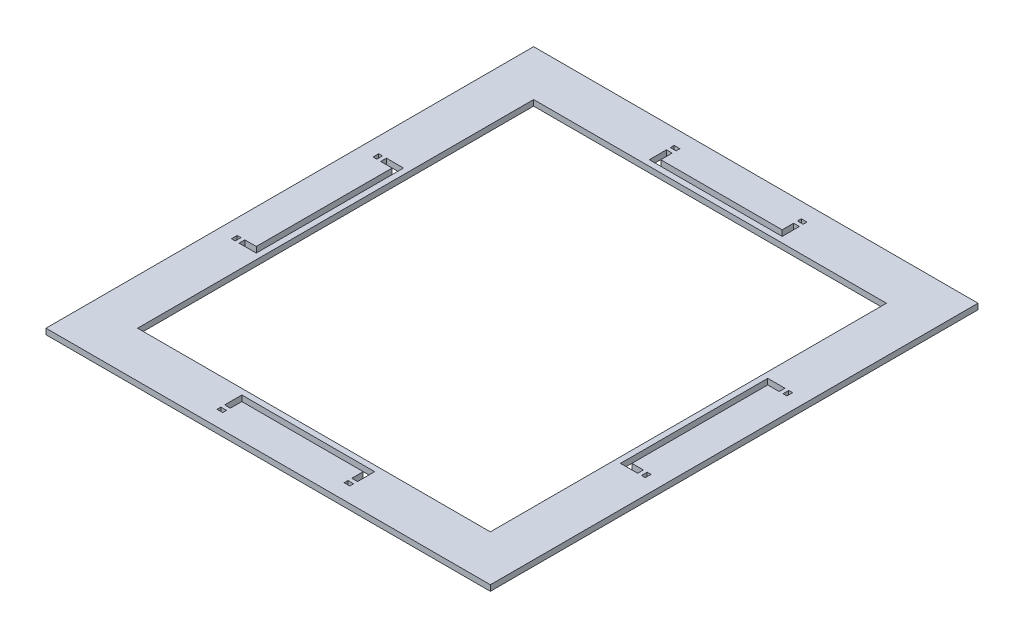
SolidWorks part; units mm, degrees
material "Delrin 2700 NC010, Low Viscosity Acetal Copolymer (SS)"
ref_plane "Front Plane" through (0, 0, 0) normal (0, 0, 1) x (1, 0, 0)
ref_plane "Top Plane" through (0, 0, 0) normal (0, 1, 0) x (1, 0, 0)
ref_plane "Right Plane" through (0, 0, 0) normal (1, 0, 0) x (0, 0, -1)
sketch "Sketch1" plane through (0, 0, 0) normal (0, 1, 0) x (1, 0, 0)
  line L0 (0, 135.225) -> (0, 0)
  line L1 (-110.525, 122.525) -> (0, 122.525)
  line L2 (-36.8417, 126.7583) -> (-33.6667, 126.7583)
  line L3 (-123.225, 135.225) -> (0, 135.225)
  line L4 (-123.225, 135.225) -> (-123.225, 0)
  line L5 (-36.8417, 126.7583) -> (-36.8417, 124.6417)
  line L6 (-36.8417, 124.6417) -> (-33.6667, 124.6417)
  line L7 (-33.6667, 126.7583) -> (-33.6667, 124.6417)
  line L8 (-114.7583, 40.8417) -> (-112.6417, 40.8417)
  line L9 (-114.7583, 40.8417) -> (-114.7583, 37.6667)
  line L10 (-114.7583, 37.6667) -> (-112.6417, 37.6667)
  line L11 (-112.6417, 40.8417) -> (-112.6417, 37.6667)
  line L12 (-110.525, 0) -> (-110.525, 122.525)
  line L13 (-110.525, 0) -> (-104.175, 0)
  line L14 (-110.525, 0) -> (-110.525, 37.6667)
  line L15 (-110.525, 37.6667) -> (-104.175, 37.6667)
  line L16 (-104.175, 0) -> (-104.175, 37.6667)
  line L17 (-110.525, 40.8417) -> (-101, 40.8417)
  line L18 (-110.525, 40.8417) -> (-110.525, 122.525)
  line L19 (-110.525, 122.525) -> (-78.9277, 122.525)
  line L20 (-101, 40.8417) -> (-101, 113)
  line L21 (-36.8417, 122.525) -> (-78.9277, 122.525)
  line L22 (-36.8417, 122.525) -> (-36.8417, 113)
  line L23 (-36.8417, 113) -> (-101, 113)
  line L24 (0, 122.525) -> (-33.6667, 122.525)
  line L25 (0, 122.525) -> (0, 116.175)
  line L26 (0, 116.175) -> (-33.6667, 116.175)
  line L27 (-33.6667, 122.525) -> (-33.6667, 116.175)
  line L28 (0, 0) -> (-123.225, 0)
  point P12 (0, 122.525)
  dimension "D1" = 12.7
  dimension "D2" = 2.1167
  dimension "D3" = 3.175
  dimension "D4" = 2.1167
  dimension "D5" = 2.1167
  dimension "D6" = 3.175
  dimension "D7" = 9.525
  dimension "D8" = 0
  dimension "D9" = 0
  dimension "D10" = 0
  dimension "D11" = 6.35
  dimension "D12" = 0
  dimension "D13" = 9.525
  dimension "D14" = 12.7
  dimension "D15" = 2.1167
  dimension "D16" = 6.35
  dimension "D17" = 104.175
  dimension "D18" = 67.3333
  dimension "D19" = 75.3333
  dimension "D21" = 116.175
extrude "Boss-Extrude1" add sketch "Sketch1" along normal blind 3.175 contours L28 L12 L1 L0 L3 L4 L8 L11 L10 L9 L2 L7 L6 L5 | L13 L16 L15 L12 | L23 L22 L1 L12 L17 L20 | L1 L27 L26 L0 region at (-1.8295, 0, -128.875) region at (-16.8333, 0, -119.35) region at (-37.9417, 0, -117.7625) region at (-107.35, 0, -18.8333)
sketch "Sketch3" plane through (0, 3.175, 0) normal (0, 1, 0) x (1, 0, 0)
  line L0 (0, 135.225) -> (0, 116.175) construction
  line L1 (-101, 113) -> (0, 113)
  line L2 (-101, 113) -> (-101, 109.825)
  line L3 (-101, 109.825) -> (0, 109.825)
  line L4 (0, 113) -> (0, 109.825)
  line L5 (-101, 113) -> (-97.825, 113)
  line L6 (-101, 113) -> (-101, 0)
  line L7 (-101, 0) -> (-97.825, 0)
  line L8 (-97.825, 113) -> (-97.825, 0)
  dimension "D1" = 3.175
  dimension "D2" = 3.175
  dimension "D3" = 0
  dimension "D4" = 0
extrude "Boss-Extrude2" add sketch "Sketch3" against normal blind 3.175 contours L5 L8 L7 L6 | L1 L4 L3 L2
mirror "Mirror4" about plane through (0, 0, 0) normal (1, 0, 0) of "Boss-Extrude2", "Boss-Extrude1"
mirror "Mirror5" about plane through (0, 0, 0) normal (0, 0, 1) of "Mirror4"
equation "\"D4@Sketch1\"=\"D2@Sketch1\""
equation "\"D15@Sketch1\"=\"D2@Sketch1\""
equation "\"D5@Sketch1\"=\"D2@Sketch1\""
equation "\"D6@Sketch1\"=\"D3@Sketch1\""
equation "\"D16@Sketch1\"=\"D11@Sketch1\""
equation "\"D13@Sketch1\"=\"D7@Sketch1\""
equation "\"Resolution Projector X\"= 1920"
equation "\"Resolution Projector Y\"= 1080"
equation "\"Resolution Build\"= 0.1"
equation "\"Size Build Volume X\"= \"Resolution Projector X\" * \"Resolution Build\""
equation "\"Size Build Volume Y\"= 2 * \"Resolution Projector Y\" * \"Resolution Build\""
equation "\"Size Build Volume Z\"= \"Size Build Volume Y\""
equation "\"Size Enclosure Internal X\"= 350mm"
equation "\"Size Enclosure Internal Y\"= \"Size Enclosure Internal X\""
equation "\"Size Enclosure Internal Z\"= \"Size Enclosure Internal X\""
equation "\"Size Enclosure External Z\"= 1000mm"
equation "\"Clearance Vat\"= 10mm'd_ clearance vat data"
equation "\"Size Vat X\"= \"Size Build Volume X\" + \"Clearance Vat\"'f_ size vat data"
equation "\"Size Vat Y\"= \"Size Build Volume Y\" + \"Clearance Vat\"'f_ size vat data"
equation "\"Size Vat Z\"= \"Size Build Volume Z\" + \"Clearance Vat\"'f_ size vat data"
equation "\"Thickness Vat\"= 3.175mm'g_ thickness vat data"
equation "\"width rib\"= 2 * \"Thickness Vat\"'g_ thickness of the Rib"
equation "\"width Lip on rib\"= \"Thickness Vat\" * 2'g_ thickness of the lip connected to the tab"
equation "\"height Lip on rib\"= \"width Lip on rib\"'g_ height of lip on rib structure"
equation "\"height adjustment\"= \"Thickness Vat\" * 2'g_ height adjustment for lip.  This flushes the top part of the tab to top of the walls"
equation "\"goofy tab x\"= \"Size Vat X\" * ( 1 / 3 ) - \"width rib\"'h_ goofy slot found on rib X"
equation "\"goofy tab y\"= \"Size Vat Y\" * ( 1 / 3 ) - \"width rib\"'h_ goofy slot found on rib Y"
equation "\"D3@Sketch1\"=\"Thickness Vat\""
equation "\"D18@Sketch1\"=\"Size Vat X\"/3"
equation "\"D19@Sketch1\"=\"Size Vat Y\"/3"
equation "\"D1@Sketch1\"=\"width Lip on rib\"*2mm"
equation "\"D14@Sketch1\"=\"D1@Sketch1\""
equation "\"D11@Sketch1\"=\"Thickness Vat\"*2"
equation "\"D7@Sketch1\"=\"Thickness Vat\"*3"
equation "\"D17@Sketch1\"=\"Size Vat X\"/2 + \"Thickness Vat\""
equation "\"D21@Sketch1\"=\"Size Vat Y\"/2 + \"Thickness Vat\""
equation "\"D1@Boss-Extrude1\"=\"Thickness Vat\""
equation "\"D1@Sketch3\"=\"Thickness Vat\""
equation "\"D2@Sketch3\"=\"Thickness Vat\""
equation "\"D1@Boss-Extrude2\"=\"Thickness Vat\""
